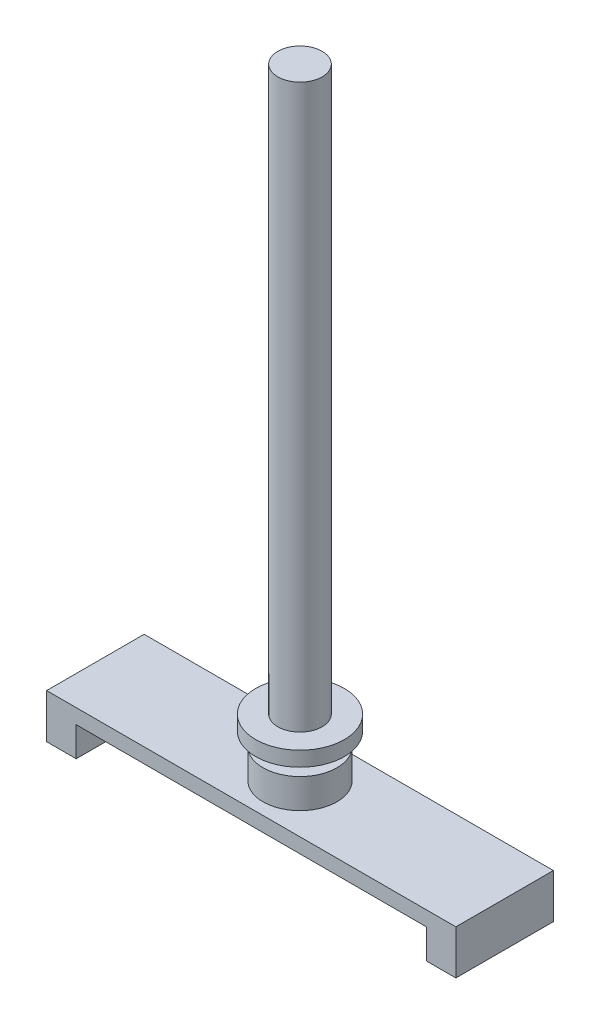
SolidWorks part; units mm, degrees
ref_plane "Front Plane" through (0, 0, 0) normal (0, 0, 1) x (1, 0, 0)
ref_plane "Top Plane" through (0, 0, 0) normal (0, 1, 0) x (1, 0, 0)
ref_plane "Right Plane" through (0, 0, 0) normal (1, 0, 0) x (0, 0, -1)
sketch "Sketch1" plane through (0, 0, 0) normal (0, 0, 1) x (1, 0, 0)
  line L0 (0, 0) -> (0, 50.8284) construction
  line L1 (-138.5, 0) -> (138.5, 0)
  line L2 (138.5, 0) -> (138.5, -30)
  line L3 (138.5, -30) -> (118.5, -30)
  line L4 (118.5, -30) -> (118.5, -10)
  line L5 (118.5, -10) -> (-118.5, -10)
  line L6 (-138.5, 0) -> (-138.5, -30)
  line L7 (-138.5, -30) -> (-118.5, -30)
  line L8 (-118.5, -30) -> (-118.5, -10)
  point P6 (0, 0)
  point P13 (0, -10)
  dimension "D1" = 277
  dimension "D2" = 20
extrude "Boss-Extrude1" add sketch "Sketch1" along normal blind 33 and the other way blind 33
sketch "Sketch2" plane through (0, -30, 0) normal (0, -1, 0) x (1, 0, 0)
  line L0 (-138.5, 33) -> (-118.5, 33) construction
  line L1 (-133.5, 31.5) -> (-123.5, 31.5)
  line L2 (-133.5, 31.5) -> (-133.5, -31.5)
  line L3 (-133.5, -31.5) -> (-123.5, -31.5)
  line L4 (-123.5, 31.5) -> (-123.5, -31.5)
  line L5 (-133.5, 31.5) -> (-123.5, -31.5) construction
  line L6 (-133.5, -31.5) -> (-123.5, 31.5) construction
  line L7 (-138.5, -33) -> (-138.5, 33) construction
  line L8 (0, 0) -> (0, -33) construction
  line L9 (-118.5, -33) -> (118.5, -33) construction
  line L10 (133.5, -31.5) -> (123.5, -31.5)
  line L11 (123.5, 31.5) -> (123.5, -31.5)
  line L12 (133.5, 31.5) -> (123.5, 31.5)
  line L13 (133.5, 31.5) -> (133.5, -31.5)
  point P0 (-128.5, 0)
  point P11 (-128.5, 33)
  point P15 (-138.5, 0)
extrude "Cut-Extrude1" cut sketch "Sketch2" against normal blind 20
sketch "Sketch3" plane through (0, 0, 0) normal (0, 1, 0) x (1, 0, 0)
  circle A0 centre (0, 0) radius 25
extrude "Boss-Extrude2" add sketch "Sketch3" along normal blind 20
sketch "Sketch4" plane through (0, 20, 0) normal (0, 1, 0) x (1, 0, 0)
  circle A0 centre (0, 0) radius 15
extrude "Boss-Extrude3" add sketch "Sketch4" along normal blind 400
ref_plane "Plane1" through (0, 29, 0) normal (0, 1, 0) x (1, 0, 0)
sketch "Sketch5" plane through (0, 29, 0) normal (0, 1, 0) x (1, 0, 0)
  circle A0 centre (0, 0) radius 30
extrude "Boss-Extrude4" add sketch "Sketch5" along normal blind 10
